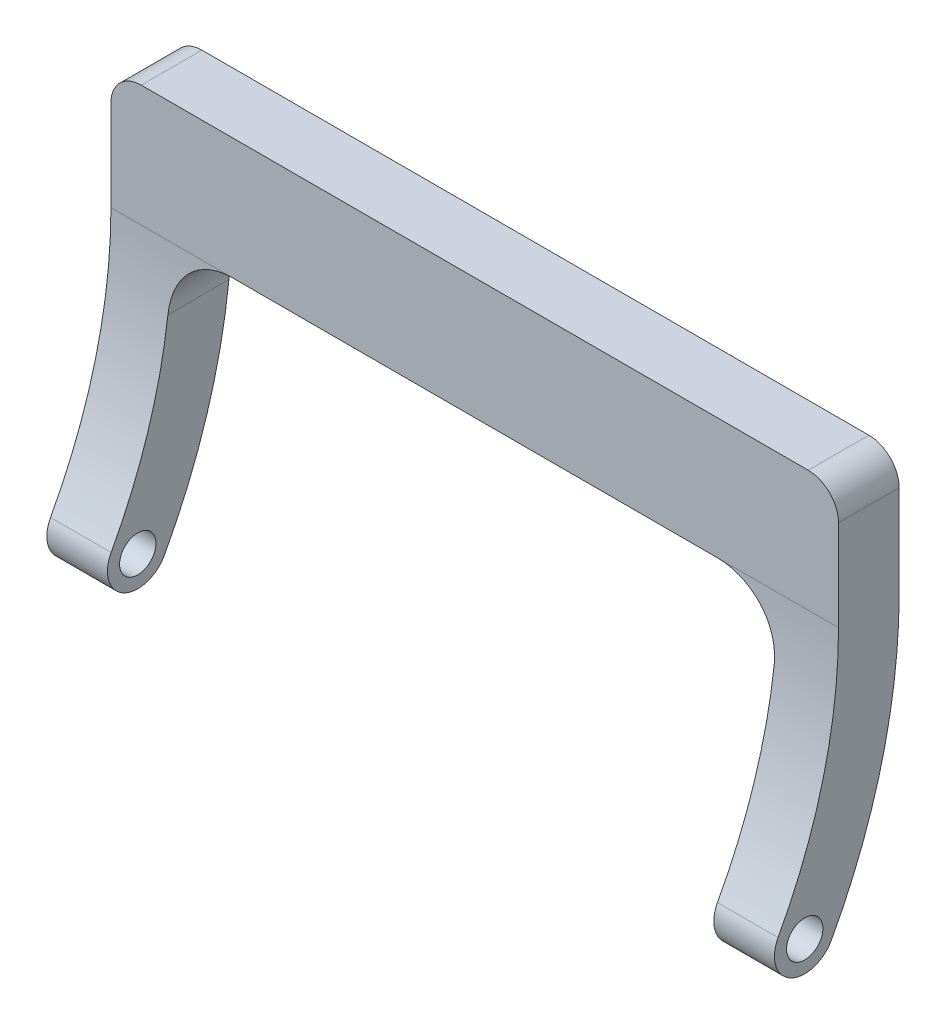
SolidWorks part; units mm, degrees
ref_plane "Plan de face" through (0, 0, 0) normal (0, 0, 1) x (1, 0, 0)
ref_plane "Plan de dessus" through (0, 0, 0) normal (0, 1, 0) x (1, 0, 0)
ref_plane "Plan de droite" through (0, 0, 0) normal (1, 0, 0) x (0, 0, -1)
sketch "Esquisse2" plane through (0, 0, 0) normal (0, 0, 1) x (1, 0, 0)
  line L1 (-27.5, 5) -> (27.5, 5)
  line L2 (-30, 2.5) -> (-30, -5)
  line L3 (-30, -5) -> (30, -5)
  line L4 (30, 2.5) -> (30, -5)
  line L5 (-30, 5) -> (30, -5) construction
  line L6 (-30, -5) -> (30, 5) construction
  arc A0 (27.5, 5) -> (30, 2.5) centre (27.5, 2.5) cw
  arc A1 (-27.5, 5) -> (-30, 2.5) centre (-27.5, 2.5) ccw
  point P0 (0, 0)
  dimension "D3" = 2.5
  dimension "D1" = 60
  dimension "D2" = 10
extrude "Boss.-Extru.1" add sketch "Esquisse2" along normal blind 5
sketch "Esquisse3" plane through (-30, 0, 0) normal (-1, 0, 0) x (0, 0, 1)
  line L0 (0, 2.5) -> (0, -5) construction
  line L1 (0, -5) -> (5, -5)
  arc A0 (0, -5) -> (5.5907, -27.021) centre (46.1644, -5) ccw
  arc A1 (5, -5) -> (9.9852, -24.636) centre (46.1644, -5) ccw
  arc A2 (5.5907, -27.021) -> (9.9852, -24.636) centre (7.7879, -25.8285) ccw
  circle A3 centre (7.7879, -25.8285) radius 1.5
  line M6 (0, -5) -> (5, -5)
  dimension "D1" = 5
  dimension "D2" = 3
extrude "Boss.-Extru.2" add sketch "Esquisse3" against normal blind 5 contours A0 A2 A1 A3 M6 region at (-30, -15.9796, 4.364)
mirror "Symétrie1" about plane through (0, 0, 0) normal (1, 0, 0) of "Boss.-Extru.2"
fillet "Congé1" radius 5 2 edges at (-25, -5, 2.5) (25, -5, 2.5)
sketch "Esquisse4" plane through (0, 0, 0) normal (0, 0, -1) x (-1, 0, 0)
  line L0 (0, 5) -> (0, -5) construction
  line L1 (20, -5) -> (-20, -5) construction
  line L2 (-27.5, 5) -> (27.5, 5) construction
  line L3 (-20, 0) -> (20, 0) construction
  circle A0 centre (-20, 0) radius 2
  circle A1 centre (20, 0) radius 2
  point P10 (0, 0)
  dimension "D2" = 4
  dimension "D3" = 4
  dimension "D1" = 40
extrude "Enlèv. mat.-Extru.1" cut sketch "Esquisse4" against normal blind 2 from offset 1.5 offset against normal yes
